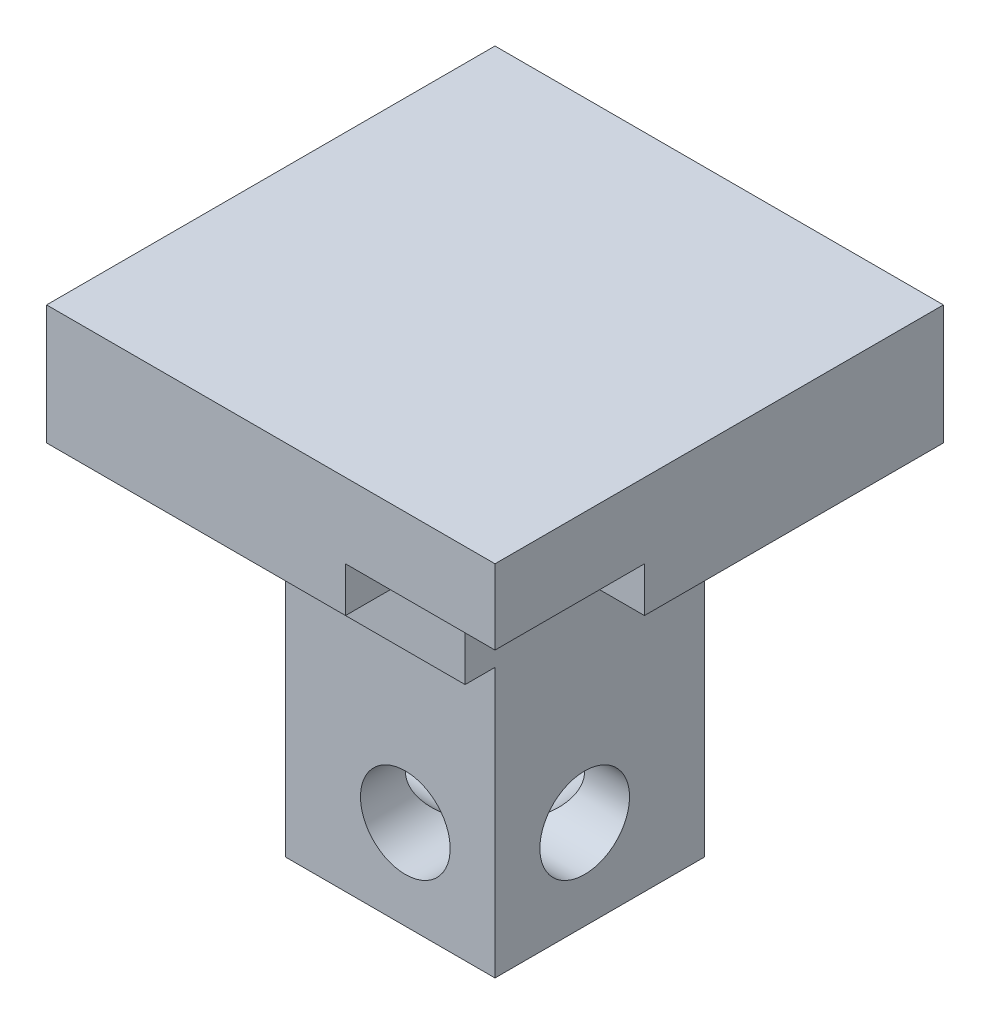
SolidWorks part; units mm, degrees
ref_plane "Front" through (0, 0, 0) normal (0, 0, 1) x (1, 0, 0)
ref_plane "Top" through (0, 0, 0) normal (0, 1, 0) x (1, 0, 0)
ref_plane "Right" through (0, 0, 0) normal (1, 0, 0) x (0, 0, -1)
sketch "Szkic1" plane through (0, 0, 0) normal (1, 0, 0) x (0, 0, -1)
  line L1 (-8, -6) -> (8, -6)
  line L2 (-8, -6) -> (-8, 34)
  line L3 (-8, 34) -> (8, 34)
  line L4 (8, -6) -> (8, 34)
  circle A0 centre (0, 0) radius 3
  dimension "D1" = 6
  dimension "D2" = 6
  dimension "D3" = 16
  dimension "D4" = 8
  dimension "D5" = 40
extrude "Dodanie-wyciągnięcie1" add sketch "Szkic1" along normal blind 16 contours L1 L4 L3 L2 A0 region at (0, 14.6471, 0)
sketch "Szkic2" plane through (0, 0, 8) normal (0, 0, 1) x (1, 0, 0)
  line L0 (16, -6) -> (0, -6) construction
  line L1 (0, -6) -> (0, 34) construction
  circle A0 centre (8, 0) radius 3
  dimension "D1" = 6
  dimension "D2" = 6
  dimension "D3" = 8
extrude "Wytnij-wyciągnięcie1" cut sketch "Szkic2" against normal through all
sketch "Szkic3" plane through (0, 0, 8) normal (0, 0, 1) x (1, 0, 0)
  line L0 (16, -6) -> (16, 34) construction
  line L1 (0, -6) -> (16, -6)
  line L2 (0, -6) -> (0, 12)
  line L3 (0, 12) -> (16, 12)
  line L4 (16, -6) -> (16, 12)
  dimension "D1" = 18
extrude "Wytnij-wyciągnięcie2" cut sketch "Szkic3" against normal blind 2
sketch "Szkic4" plane through (16, 0, 0) normal (1, 0, 0) x (0, 0, -1)
  line L0 (-8, 12) -> (-8, 34) construction
  line L1 (8, -6) -> (-8, -6)
  line L2 (8, -6) -> (8, 16)
  line L3 (8, 16) -> (-8, 16)
  line L4 (-8, -6) -> (-8, 16)
  dimension "D1" = 22
extrude "Wytnij-wyciągnięcie3" cut sketch "Szkic4" against normal blind 2
sketch "Szkic5" plane through (0, 34, 0) normal (0, 1, 0) x (1, 0, 0)
  line L1 (0, 8) -> (30, 8)
  line L2 (0, 8) -> (0, -22)
  line L3 (0, -22) -> (30, -22)
  line L4 (30, 8) -> (30, -22)
  dimension "D1" = 30
  dimension "D2" = 30
extrude "Dodanie-wyciągnięcie2" add sketch "Szkic5" against normal blind 5
fillet "Zaokrąglenie1" radius 2 2 edges at (8, 29, 8) (16, 29, 0)
sketch "Szkic6" plane through (0, 29, 0) normal (0, -1, 0) x (1, 0, 0)
  line L0 (30, 22) -> (30, -8) construction
  line L1 (0, 22) -> (20, 22)
  line L2 (0, 22) -> (0, 19)
  line L3 (0, 19) -> (20, 19)
  line L4 (20, 22) -> (20, 19)
  line L5 (30, -8) -> (27, -8)
  line L6 (30, -8) -> (30, 12)
  line L7 (30, 12) -> (27, 12)
  line L8 (27, -8) -> (27, 12)
  dimension "D1" = 3
  dimension "D2" = 3
  dimension "D3" = 20
  dimension "D4" = 20
extrude "Dodanie-wyciągnięcie3" add sketch "Szkic6" along normal blind 3
